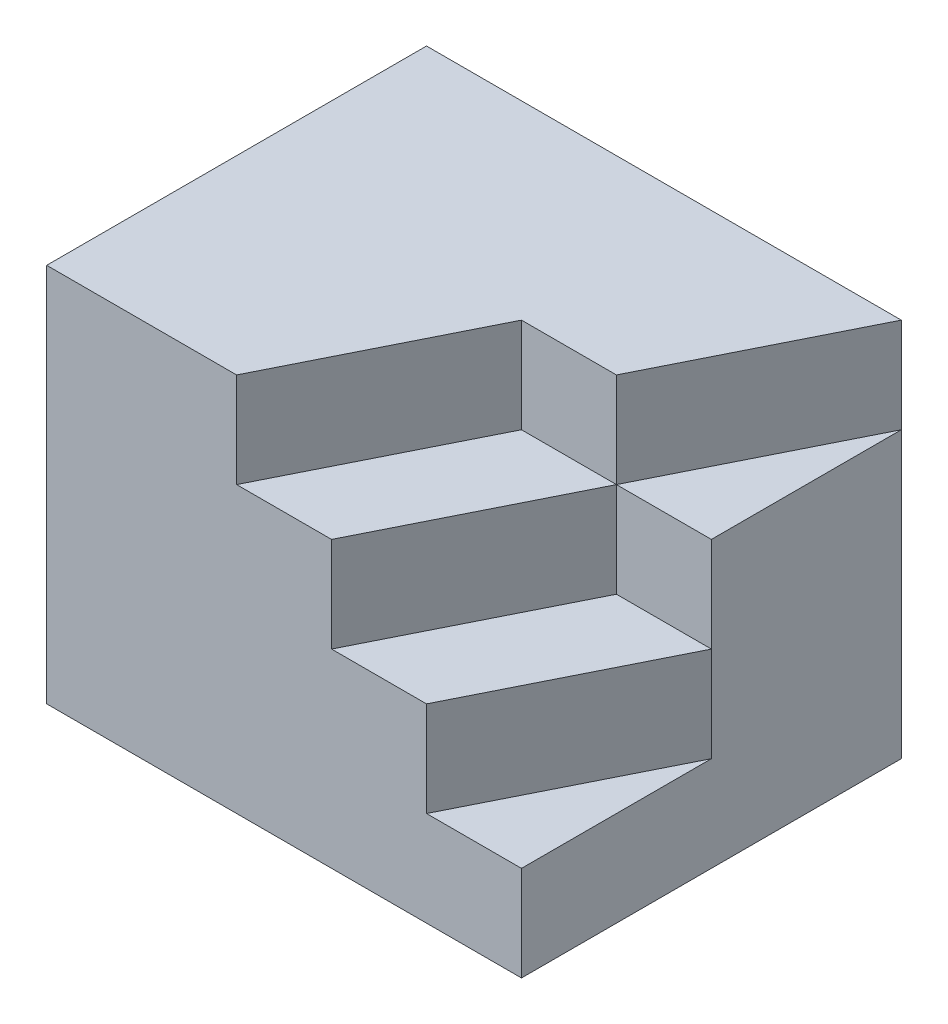
SolidWorks part; units mm, degrees
ref_plane "前基準面" through (0, 0, 0) normal (0, 0, 1) x (1, 0, 0)
ref_plane "上基準面" through (0, 0, 0) normal (0, 1, 0) x (1, 0, 0)
ref_plane "右基準面" through (0, 0, 0) normal (1, 0, 0) x (0, 0, -1)
sketch "草圖1" plane through (0, 0, 0) normal (0, 1, 0) x (1, 0, 0)
  line L0 (2.5, 0) -> (-2.5, -10)
  line L1 (12.5, 10) -> (-12.5, 10)
  line L2 (12.5, 10) -> (12.5, -10)
  line L3 (12.5, -10) -> (-12.5, -10)
  line L4 (-12.5, 10) -> (-12.5, -10)
  line L5 (12.5, 10) -> (-12.5, -10) construction
  line L6 (12.5, -10) -> (-12.5, 10) construction
  line L7 (-2.5, -10) -> (7.5, -10)
  line L8 (7.5, -10) -> (12.5, 0)
  line L9 (12.5, 0) -> (2.5, 0)
  line L10 (2.5, 0) -> (7.5, 0)
  line L11 (7.5, 0) -> (2.5, -10)
  line L12 (7.5, 0) -> (12.5, 10)
  point P0 (0, 0)
  dimension "D1" = 25
  dimension "D2" = 20
  dimension "D3" = 5
  dimension "D4" = 5
  dimension "D5" = 5
  dimension "D6" = 5
  dimension "D7" = 5
  dimension "D8" = 10
extrude "填料-伸長1" add sketch "草圖1" along normal blind 5 contours L8 L3 L2 | L9 L11 L3 L8 | L11 L9 L0 L7 | L9 L12 L1 L4 L3 L0 | L12 L9 L2 region at (2.5, 0, 5) region at (-2.9762, 0, -1.6667) region at (10.8333, 0, -3.3333) region at (7.5, 0, 5) region at (10.8333, 0, 6.6667)
extrude "填料-伸長2" add sketch "草圖1<3>" along normal blind 10 contours L9 L11 L3 L8 | L12 L9 L2 | L11 L9 L0 L7 | L9 L12 L1 L4 L3 L0 region at (2.5, 0, 5) region at (-2.9762, 0, -1.6667) region at (10.8333, 0, -3.3333) region at (7.5, 0, 5)
sketch "草圖1<3>" plane through (0, 0, 0) normal (0, 1, 0) x (1, 0, 0) same geometry as "草圖1"
extrude "填料-伸長4" add sketch "草圖1<5>" along normal blind 20 contours L9 L12 L1 L4 L3 L0 region at (-2.9762, 0, -1.6667)
sketch "草圖1<5>" plane through (0, 0, 0) normal (0, 1, 0) x (1, 0, 0) same geometry as "草圖1"
extrude "填料-伸長5" add sketch "草圖1<6>" along normal blind 15 contours L12 L9 L2 | L11 L9 L0 L7 region at (2.5, 0, 5) region at (10.8333, 0, -3.3333)
sketch "草圖1<6>" plane through (0, 0, 0) normal (0, 1, 0) x (1, 0, 0) same geometry as "草圖1"
scale "縮放比例1" scale about centroid uniform scaling yes scale factor 0.2
